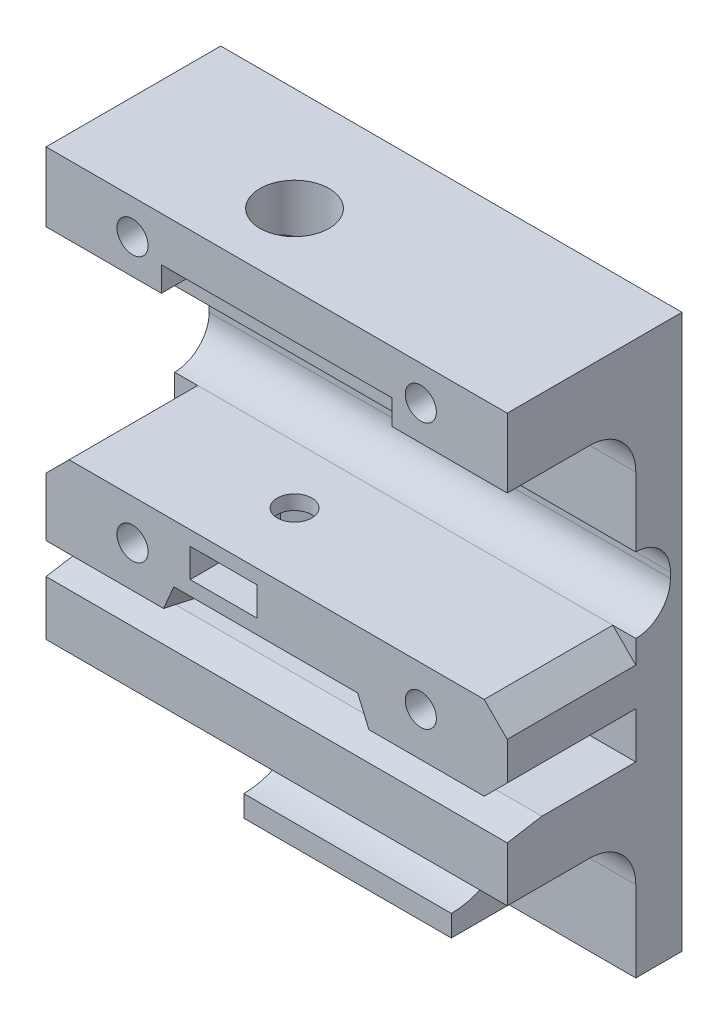
SolidWorks part; units mm, degrees
material "ABS"
ref_plane "Front Plane" through (0, 0, 0) normal (0, 0, 1) x (1, 0, 0)
ref_plane "Top Plane" through (0, 0, 0) normal (0, 1, 0) x (1, 0, 0)
ref_plane "Right Plane" through (0, 0, 0) normal (1, 0, 0) x (0, 0, -1)
sketch "Sketch1" plane through (0, 0, 0) normal (0, 0, 1) x (1, 0, 0)
  line L1 (-23.7591, 22) -> (52.715, 22) construction
  line L2 (0, -10) -> (0, 38)
  line L3 (0, 38) -> (40, 38)
  line L4 (40, -10) -> (40, 38)
  line L6 (0, -10) -> (40, -10)
  point P2 (0, 22)
  point P9 (40, 22)
  point P10 (0, 22)
  point P13 (40, 22)
  dimension "D1" = 48
  dimension "D2" = 40
extrude "Boss-Extrude1" add sketch "Sketch1" along normal blind 4
ref_plane "Plane2" through (0, 13, 0) normal (0, -1, 0) x (1, 0, 0)
sketch "Sketch2" plane through (0, 0, 4) normal (0, 0, 1) x (1, 0, 0)
  line L0 (20, 38) -> (20, 20.7808) construction
  line L1 (15.9, 33) -> (24.1, 33)
  line L2 (15.9, 33) -> (15.9, 23)
  line L3 (15.9, 23) -> (24.1, 23)
  line L4 (24.1, 33) -> (24.1, 23)
  line L5 (40, 38) -> (0, 38) construction
  line L6 (-2.2, 13) -> (2.2, 13) construction
  line L9 (2, 3) -> (10.2, 3)
  line L10 (2, 3) -> (2, -7)
  line L11 (2, -7) -> (10.2, -7)
  line L12 (10.2, 3) -> (10.2, -7)
  line L14 (29.8, 3) -> (29.8, -7)
  line L15 (38, -7) -> (29.8, -7)
  line L16 (38, 3) -> (38, -7)
  line L17 (38, 3) -> (29.8, 3)
  line L18 (15.9, 28) -> (24.1, 28) construction
  line L19 (2, -2) -> (38, -2) construction
  dimension "D1" = 8.2
  dimension "D2" = 10
  dimension "D3" = 20
  dimension "D4" = 4.1
  dimension "D5" = 30
  dimension "D6" = 2
extrude "Cut-Extrude1" [suppressed] cut sketch "Sketch2" against normal blind 1
sketch "Sketch3" [suppressed] plane through (0, 0, 3) normal (0, 0, 1) x (1, 0, 0)
  line L0 (15.9, 33) -> (15.9, 23) construction
  line L1 (15.9, 32.1) -> (24.1, 32.1)
  line L2 (15.9, 32.1) -> (15.9, 23.9)
  line L3 (15.9, 23.9) -> (24.1, 23.9)
  line L4 (24.1, 32.1) -> (24.1, 23.9)
  line L5 (24.1, 23) -> (24.1, 33) construction
  line L6 (24.1, 33) -> (15.9, 33) construction
  line L7 (15.9, 23) -> (24.1, 23) construction
  line L8 (2, 3) -> (2, -7) construction
  line L9 (2, 2.1) -> (10.2, 2.1)
  line L10 (2, 2.1) -> (2, -6.1)
  line L11 (2, -6.1) -> (10.2, -6.1)
  line L12 (10.2, 2.1) -> (10.2, -6.1)
  line L13 (10.2, -7) -> (10.2, 3) construction
  line L14 (29.8, 3) -> (29.8, -7) construction
  line L15 (29.8, 2.1) -> (38, 2.1)
  line L16 (29.8, 2.1) -> (29.8, -6.1)
  line L17 (29.8, -6.1) -> (38, -6.1)
  line L18 (38, 2.1) -> (38, -6.1)
  line L19 (38, -7) -> (38, 3) construction
  line L20 (2, -7) -> (10.2, -7) construction
  dimension "D1" = 0.9
  dimension "D2" = 0.9
  dimension "D3" = 0.9
extrude "Cut-Extrude2" [suppressed] cut sketch "Sketch3" against normal blind 4
chamfer "Chamfer1" [suppressed] distance 1 angle 45
sketch "Sketch4" [suppressed] plane through (0, 0, 3) normal (0, 0, 1) x (1, 0, 0)
  line L0 (24.1, 35.1) -> (15.9, 35.1) construction
  line L1 (15.9, 35.1) -> (15.9, 26.9) construction
  line L2 (2, 1) -> (38, 1) construction
  line L3 (2, 5.1) -> (2, -3.1) construction
  line L4 (38, -7) -> (38, 3) construction
  line L5 (6.1, 2.1) -> (6.1, -3.1) construction
  line L7 (2, -3.1) -> (10.2, -3.1) construction
  line L8 (33.9, 2.1) -> (33.9, -3.1) construction
  line L10 (29.8, -3.1) -> (38, -3.1) construction
  line L12 (10.2, 2.1) -> (2, 2.1) construction
  line L13 (38, 2.1) -> (29.8, 2.1) construction
  circle A0 centre (20, 31) radius 1.65
  circle A1 centre (6.1, 1) radius 1.65
  circle A2 centre (33.9, 1) radius 1.65
  dimension "D1" = 3.3
  dimension "D2" = 4.1
  dimension "D3" = 4.1
extrude "Cut-Extrude3" [suppressed] cut sketch "Sketch4" against normal through all
ref_plane "Plane1" through (20, 0, 0) normal (1, 0, 0) x (0, 0, -1)
sketch "Sketch5" plane through (0, 0, 4) normal (0, 0, 1) x (1, 0, 0)
  line L0 (-5.9966, 13) -> (42.103, 13) construction
  line L1 (0.9, 8.125) -> (0, 8.125)
  line L2 (40, 6.225) -> (40, 1)
  line L3 (0, 6.225) -> (40, 6.225)
  line L4 (40, 15.5) -> (40, 8.225)
  line L5 (40, 8.225) -> (28, 8.225)
  line L6 (20, -2.2) -> (20, 2.2) construction
  line L7 (0, -10) -> (40, -10) construction
  line L8 (0, 1) -> (40, 1)
  line L9 (27.025, 10.5) -> (11.0812, 10.5)
  line L10 (28, 8.225) -> (27.025, 10.5)
  line L11 (5.9219, 8.125) -> (6.2219, 7.425)
  line L12 (11.0812, 10.5) -> (9.7634, 7.425)
  line L13 (6.2219, 7.425) -> (7.2317, 7.425)
  line L14 (-2.2, 13) -> (2.2, 13) construction
  line L15 (7.2317, 7.425) -> (7.5317, 8.125)
  line L16 (8.5004, 8.125) -> (8.8004, 7.425)
  line L17 (8.8004, 7.425) -> (9.7634, 7.425)
  line L18 (5.9219, 8.125) -> (5, 8.125)
  line L23 (1.2, 7.425) -> (0.9, 8.125)
  line L27 (2.5, 8.125) -> (2.2, 7.425)
  line L28 (2.2, 7.425) -> (1.2, 7.425)
  line L29 (11, -10) -> (29, -10)
  line L30 (3.7, 7.425) -> (3.4, 8.125)
  line L31 (3.4, 8.125) -> (2.5, 8.125)
  line L32 (5, 8.125) -> (4.7, 7.425)
  line L33 (4.7, 7.425) -> (3.7, 7.425)
  line L34 (11, -10) -> (11, -5)
  line L36 (8.5004, 8.125) -> (7.5317, 8.125)
  line L40 (40, -10) -> (40, 38) construction
  line L42 (40, 15.5) -> (0, 15.5)
  line L43 (0, 15.5) -> (0, 8.125)
  line L46 (0, 38) -> (0, -10) construction
  line L47 (0, 32) -> (40, 32)
  line L48 (0, 32) -> (0, 38)
  line L49 (11, -5) -> (29, -5)
  line L50 (40, 32) -> (40, 38)
  line L51 (0, 38) -> (40, 38)
  line L52 (29, -10) -> (29, -5)
  line L53 (40, 38) -> (0, 38) construction
  line L62 (0, 6.225) -> (0, 1)
  point P84 (20, 6.225)
  dimension "D2" = 0.7
  dimension "D3" = 0.9
  dimension "D4" = 0.3
  dimension "D5" = 0.3
  dimension "D7" = 1
  dimension "D9" = 5
  dimension "D10" = 4.775
  dimension "D11" = 1.9
  dimension "D14" = 18
  dimension "D15" = 5
  dimension "D19" = 2.5
  dimension "D8" = 4.875
  dimension "D12" = 12
  dimension "D13" = 12
  dimension "D6" = 19
extrude "Boss-Extrude2" add sketch "Sketch5" along normal blind 11.15 and the other way up to surface (4 mm away) other way up to face at (20, 14, 0)
fillet "Fillet1" radius 4 2 edges at (20, 32, 4) (20, 1, 4) tangent propagation no
sketch "Sketch6" plane through (0, 0, 15.15) normal (0, 0, 1) x (1, 0, 0)
  line L0 (7.5, 41.1026) -> (7.5, 12.7734) construction
  line L2 (20, 38) -> (20, 13.7163) construction
  line L3 (20, -2.2) -> (20, 2.2) construction
  line L4 (-2.2, 13) -> (2.2, 13) construction
  line L6 (40, 38) -> (0, 38) construction
  circle A0 centre (7.5, 35) radius 1.35
  circle A1 centre (7.5, 12) radius 1.35
  circle A2 centre (32.5, 35) radius 1.35
  circle A3 centre (32.5, 12) radius 1.35
  dimension "D1" = 2.7
  dimension "D2" = 23
  dimension "D3" = 22
  dimension "D4" = 12.5
extrude "Cut-Extrude4" cut sketch "Sketch6" against normal through all
chamfer "Chamfer2" distance 2 angle 45 3 edges at (0, 15.5, 9.575) (40, 8.225, 9.575) (40, 15.5, 9.575)
sketch "Sketch7" plane through (0, 0, 4) normal (0, 0, 1) x (1, 0, 0)
  line L0 (0, 28) -> (0, 13.5) construction
  line L1 (0, 22) -> (40, 22)
  line L2 (0, 22) -> (0, 15.5)
  line L3 (0, 15.5) -> (40, 15.5)
  line L4 (40, 22) -> (40, 15.5)
  line L7 (38, 15.5) -> (2, 15.5) construction
  line L8 (-2.2, 13) -> (2.2, 13) construction
  dimension "D1" = 9
extrude "Cut-Extrude5" cut sketch "Sketch7" against normal blind 3
fillet "Fillet2" radius 3 2 edges at (20, 15.5, 1) (20, 22, 1)
chamfer "Chamfer3" distance 3 distance2 1 2 edges at (1.7, 7.425, 15.15) (4.2, 7.425, 15.15) first distance on face at (1.7, 7.425, 9.575) first distance on face at (4.2, 7.425, 9.575)
chamfer "Chamfer4" distance 3 distance2 0.5 1 edges at (20, 6.225, 15.15) first distance on face at (20, 6.225, 9.575)
sketch "Sketch8" plane through (20, 0, 0) normal (1, 0, 0) x (0, 0, -1)
  line L0 (-9, 28) -> (-9, -2) construction
  line L1 (-15.15, 38) -> (0, 38) construction
  line L2 (-4, 6.225) -> (-4, 10.225) construction
  line L4 (-9, 34.15) -> (-18.8563, 34.15)
  line L5 (-18.8563, 34.15) -> (-18.8563, 21.85)
  line L6 (-18.8563, 21.85) -> (-9, 21.85)
  line L8 (-18.8563, -10.4372) -> (-18.8563, -3.1589)
  line L9 (-18.8563, -3.1589) -> (-13.3487, 2.3487)
  line L10 (-9, -8.15) -> (-9, -10.4372)
  line L11 (-9, -10.4372) -> (-18.8563, -10.4372)
  arc A0 (-9, 21.85) -> (-9, 34.15) centre (-9, 28) ccw
  arc A1 (-9, -8.15) -> (-13.3487, 2.3487) centre (-9, -2) ccw
  dimension "D2" = 12.3
  dimension "D1" = 30
  dimension "D3" = 10
  dimension "D4" = 5
  dimension "D5" = 45
extrude "Cut-Extrude6" cut sketch "Sketch8" against normal blind 10 and the other way blind 10
sketch "Sketch12" plane through (0, 38, 0) normal (0, 1, 0) x (1, 0, 0)
  line L1 (10, -4) -> (0, -4) construction
  circle A0 centre (15.4, -9) radius 3
  dimension "D3" = 6
  dimension "D1" = 5
  dimension "D2" = 15.4
extrude "Cut-Extrude8" cut sketch "Sketch12" against normal up to surface (22.5 mm away) up to face at (20, 15.5, 9.575)
sketch "Sketch13" plane through (0, 15.5, 0) normal (0, 1, 0) x (1, 0, 0)
  circle A0 centre (15.4, -9) radius 1.5
  circle A1 centre (15.4, -9) radius 3 construction
  dimension "D1" = 3
extrude "Cut-Extrude10" cut sketch "Sketch13" against normal offset from surface (10.275 mm away) 1 up to face at (20, 6.225, 8.075) offset beyond the face yes
sketch "Sketch9" plane through (0, 13, 0) normal (0, -1, 0) x (1, 0, 0)
  line L0 (12.5, 16.8153) -> (18.3, 16.8153)
  line L1 (15.4, 5.6514) -> (18.3, 7.3257)
  line L2 (18.3, 7.3257) -> (18.3, 16.8153)
  line L5 (12.5, 16.8153) -> (12.5, 7.3257)
  line L6 (12.5, 7.3257) -> (15.4, 5.6514)
  line L8 (13.9872, 11.5329) -> (12.1308, 10.4612) [skipped]
  line L9 (16.8128, 11.5329) -> (14.9564, 12.6047) [skipped]
  circle A0 centre (15.4, 9) radius 2.9 construction
  arc A1 (18.4, 9) -> (12.4, 9) centre (15.4, 9) ccw construction
  dimension "D1" = 5.8
extrude "Cut-Extrude7" cut sketch "Sketch9" against normal blind 1.25 and the other way blind 1.25
